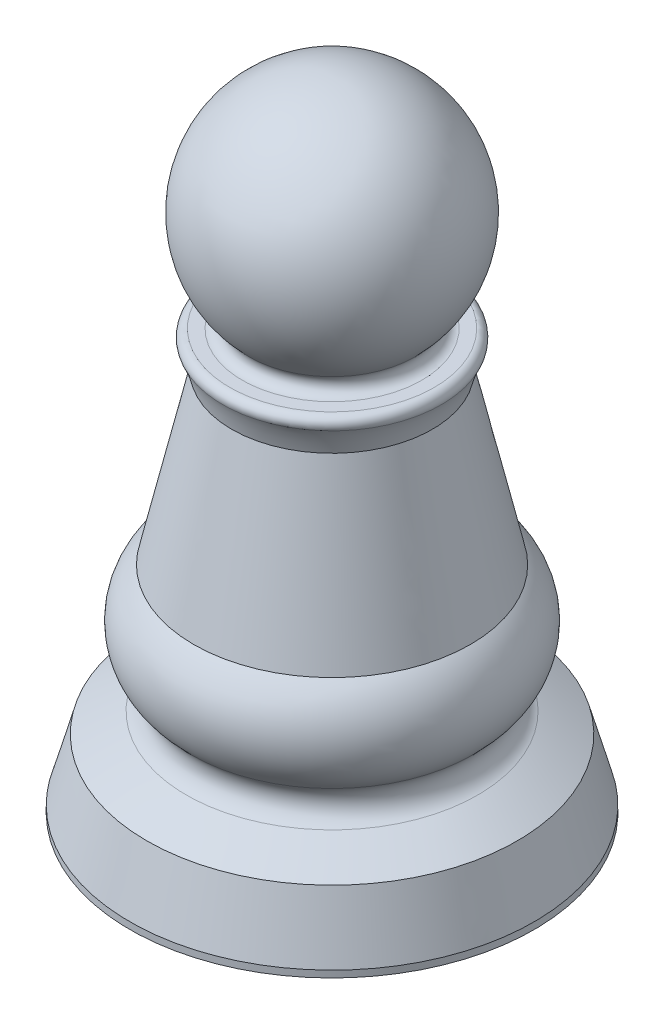
SolidWorks part; units mm, degrees
ref_plane "Front Plane" through (0, 0, 0) normal (0, 0, 1) x (1, 0, 0)
ref_plane "Top Plane" through (0, 0, 0) normal (0, 1, 0) x (1, 0, 0)
ref_plane "Right Plane" through (0, 0, 0) normal (1, 0, 0) x (0, 0, -1)
sketch "Sketch1" plane through (0, 0, 0) normal (0, 0, 1) x (1, 0, 0)
  line L0 (0, -20.6375) -> (0, 20.6375) construction
  line L1 (-13.081, -20.6375) -> (-13.081, -16.8275)
  line L2 (-13.081, -20.6375) -> (0, -20.6375)
  line L3 (-7.7956, 6.523) -> (-3.9856, 6.523)
  line L4 (0, -20.6375) -> (0, 20.6375)
  arc A0 (0, 20.6375) -> (-3.9856, 6.523) centre (0, 13.0175) ccw
  arc A1 (-6.6043, -13.8985) -> (-8.9528, -6.7214) centre (-6.35, -9.8425) cw
  spline S0 degree 2 poles (-13.081, -16.8275) (-8.6126, -14.2942) (-6.6043, -13.8985) knots 0 0 0 0.116393 0.116393 0.116393
  spline S1 degree 2 poles (-8.9528, -6.7214) (-7.7224, -1.3054) (-6.4945, 4.1112) knots 0 0 0 1 1 1
  spline S2 degree 2 poles (-6.4945, 4.1112) (-7.006, 6.2559) (-7.7956, 6.523) knots 0.860111 0.860111 0.860111 1 1 1
  point P4 (0, 0)
  dimension "D2" = 15.24
  dimension "D7" = 4.064
  dimension "D1" = 41.275
  dimension "D3" = 13.081
  dimension "D4" = 3.81
  dimension "D5" = 3.81
  dimension "D6" = 6.35
  dimension "D8" = 10.795
revolve "Revolve1" add sketch "Sketch1" angle 360 about L0
fillet "Fillet2" radius 0.635 1 edges at (0, 6.523, -3.9856)
fillet "Fillet3" radius 0.508 1 edges at (0, 6.523, -7.7956)
fillet "Fillet4" radius 1.27 1 edges at (0, -13.8985, -6.6043)
sketch "Sketch2" plane through (0, -20.6375, 0) normal (0, -1, 0) x (1, 0, 0)
  circle A0 centre (0, 0) radius 5.0165
  dimension "D1" = 10.033
extrude "Cut-Extrude1" cut sketch "Sketch2" against normal blind 2.54 from offset 0.6 offset against normal yes
chamfer "Chamfer1" distance 1.27 angle 45 1 edges at (0, -16.8275, -13.081) first distance on face at (0, -14.9208, -9.4292)
